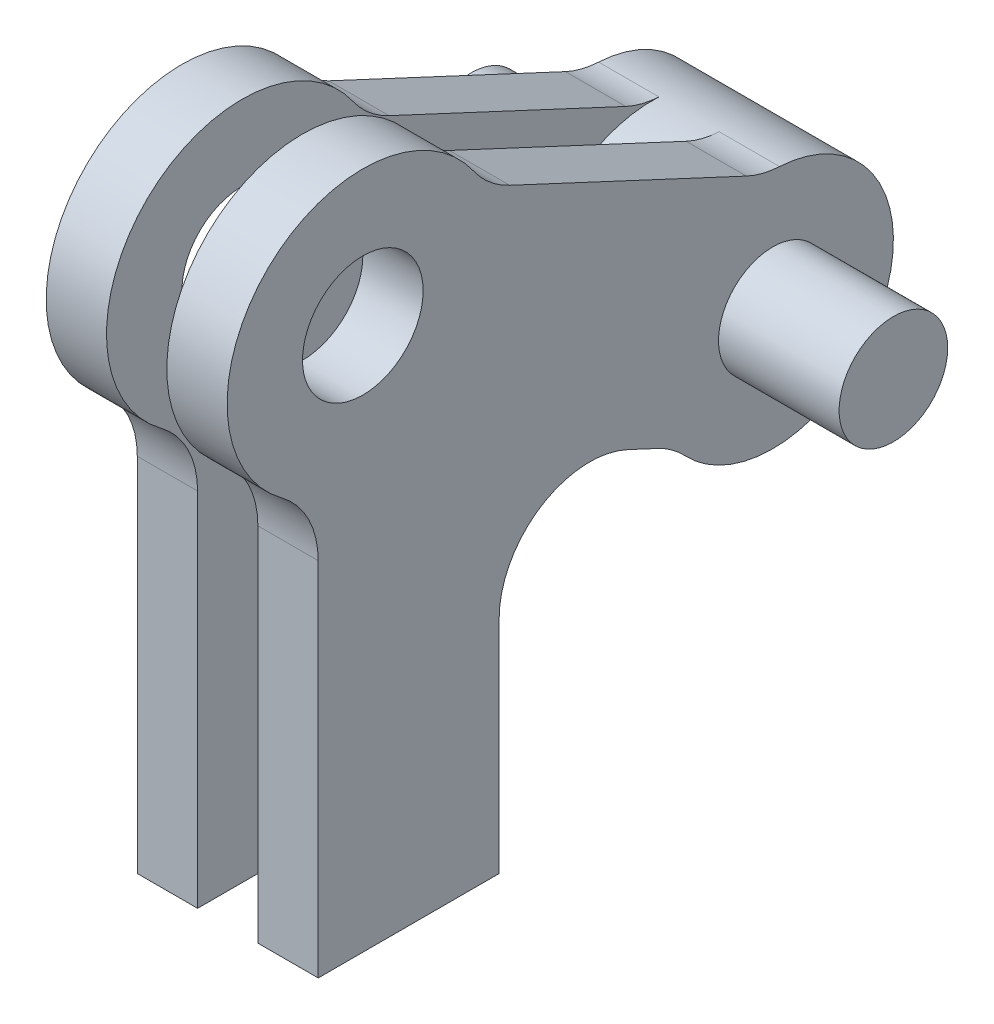
SolidWorks part; units mm, degrees
note: The reader was unsure of these and kept them because the rebuilt part matched: shared geometry of "草图1<3>", "草图1<4>", "草图2<3>", "草图2<4>".
ref_plane "前视基准面" through (0, 0, 0) normal (0, 0, 1) x (1, 0, 0)
ref_plane "上视基准面" through (0, 0, 0) normal (0, 1, 0) x (1, 0, 0)
ref_plane "右视基准面" through (0, 0, 0) normal (1, 0, 0) x (0, 0, -1)
other "Configuration Table"
sketch "草图1" plane through (0, 0, 0) normal (1, 0, 0) x (0, 0, -1)
  line L1 (-1.4792, -3.1721) -> (4.5208, -3.1721)
  line L2 (-1.4792, -3.1721) -> (-1.4792, -18)
  line L3 (-1.4792, -18) -> (4.5208, -18)
  line L4 (4.5208, -3.1721) -> (4.5208, -18)
  line L5 (-1.4792, -3.1721) -> (12.1155, -9.5114)
  line L6 (-1.4792, -3.1721) -> (1.4792, 3.1721)
  line L7 (1.4792, 3.1721) -> (15.0738, -3.1672)
  line L8 (12.1155, -9.5114) -> (15.0738, -3.1672)
  circle A0 centre (0, 0) radius 4.5
  circle A1 centre (13.5946, -6.3393) radius 4
  circle A2 centre (0, 0) radius 2
  circle A3 centre (13.5946, -6.3393) radius 2
  dimension "D4" = 9
  dimension "D5" = 8
  dimension "D8" = 4
  dimension "D1" = 65
  dimension "D2" = 18
  dimension "D3" = 6
  dimension "D6" = 7
  dimension "D7" = 15
extrude "凸台-拉伸1" add sketch "草图1" along normal blind 2 contours L6 L7 L8 L5 | A0 | A1 | L1 L4 L3 L2
extrude "切除-拉伸3" cut sketch "草图1<3>" against normal through all and the other way through all contours A2 | A3
sketch "草图1<3>" plane through (0, 0, 0) normal (1, 0, 0) x (0, 0, -1) same geometry as "草图1"
fillet "圆角1" radius 3 5 edges at (1, -4.2499, 1.4792) (1, 1.9767, -4.0426) (1, -5.9699, -4.5208) (1, -8.693, -10.3604) (1, -2.3488, -13.3187)
extrude "凸台-拉伸2" add sketch "草图1<4>" against normal blind 1 contours A3 L8 L5 A1 L7 | A3 L8 L7 A1 L5
sketch "草图1<4>" plane through (0, 0, 0) normal (1, 0, 0) x (0, 0, -1) same geometry as "草图1"
ref_plane "基准面1" through (-1, 0, 0) normal (-1, 0, 0) x (0, 0, 1)
mirror "镜向1" about plane through (-1, 0, 0) normal (-1, 0, 0) of bodies 110
sketch "草图2" plane through (2, 0, 0) normal (1, 0, 0) x (0, 0, -1)
  circle A0 centre (13.5946, -6.3393) radius 2
  circle A1 centre (13.5946, -6.3393) radius 2 construction
  circle A2 centre (13.5946, -6.3393) radius 1.8
  dimension "D1" = 3.6
extrude "凸台-拉伸3" add sketch "草图2" against normal up to surface (6 mm away) contours A0 up to face at (-4, 0, -2)
extrude "凸台-拉伸4" add sketch "草图2<3>" along normal blind 4 contours A2
sketch "草图2<3>" plane through (2, 0, 0) normal (1, 0, 0) x (0, 0, -1) same geometry as "草图2"
extrude "凸台-拉伸5" add sketch "草图2<4>" against normal blind 4 from surface contours A2 starting at face at (-4, 0, -2)
sketch "草图2<4>" plane through (2, 0, 0) normal (1, 0, 0) x (0, 0, -1) same geometry as "草图2"
equation "\"JointPoint\"= 2mm"
